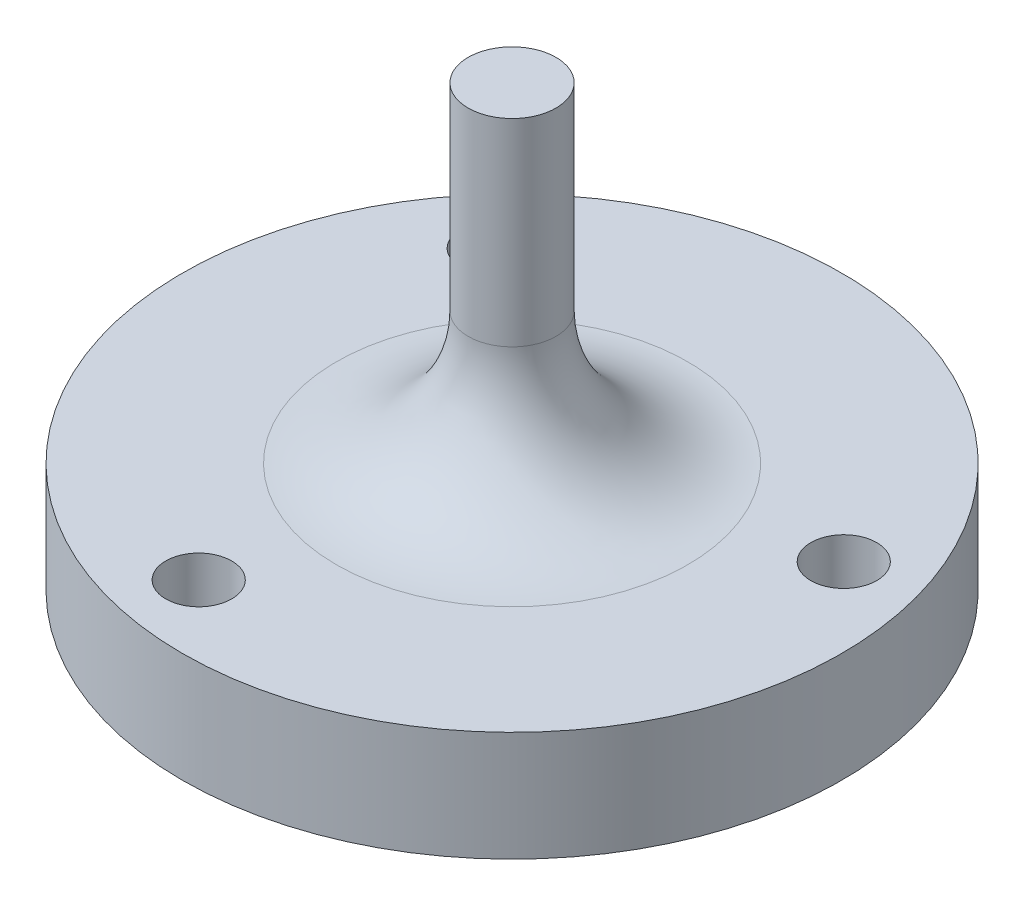
SolidWorks part; units mm, degrees
ref_plane "Front Plane" through (0, 0, 0) normal (0, 0, 1) x (1, 0, 0)
ref_plane "Top Plane" through (0, 0, 0) normal (0, 1, 0) x (1, 0, 0)
ref_plane "Right Plane" through (0, 0, 0) normal (1, 0, 0) x (0, 0, -1)
sketch "Sketch1" plane through (0, 0, 0) normal (0, 1, 0) x (1, 0, 0)
  circle A0 centre (0, 0) radius 15
  dimension "D1" = 30
extrude "Boss-Extrude1" add sketch "Sketch1" along normal blind 5
sketch "Sketch2" plane through (0, 5, 0) normal (0, 1, 0) x (1, 0, 0)
  circle A0 centre (0, 0) radius 2
  dimension "D1" = 4
extrude "Boss-Extrude2" add sketch "Sketch2" along normal blind 15
fillet "Fillet1" radius 6 1 edges at (0, 5, 2)
sketch "Sketch3" plane through (0, 5, 0) normal (0, 1, 0) x (1, 0, 0)
  circle A0 centre (-2.5321, -11.7298) radius 1.5
  circle A1 centre (0, 0) radius 15 construction
  dimension "D1" = 3
  dimension "D2" = 12
extrude "Cut-Extrude1" cut sketch "Sketch3" against normal through all
ref_axis "Axis1" through (0, 20, 0) along (0, -1, 0)
pattern_circular "CirPattern1" count 3 over 360 about axis through (0, 20, 0) along (0, -1, 0) of "Cut-Extrude1"
